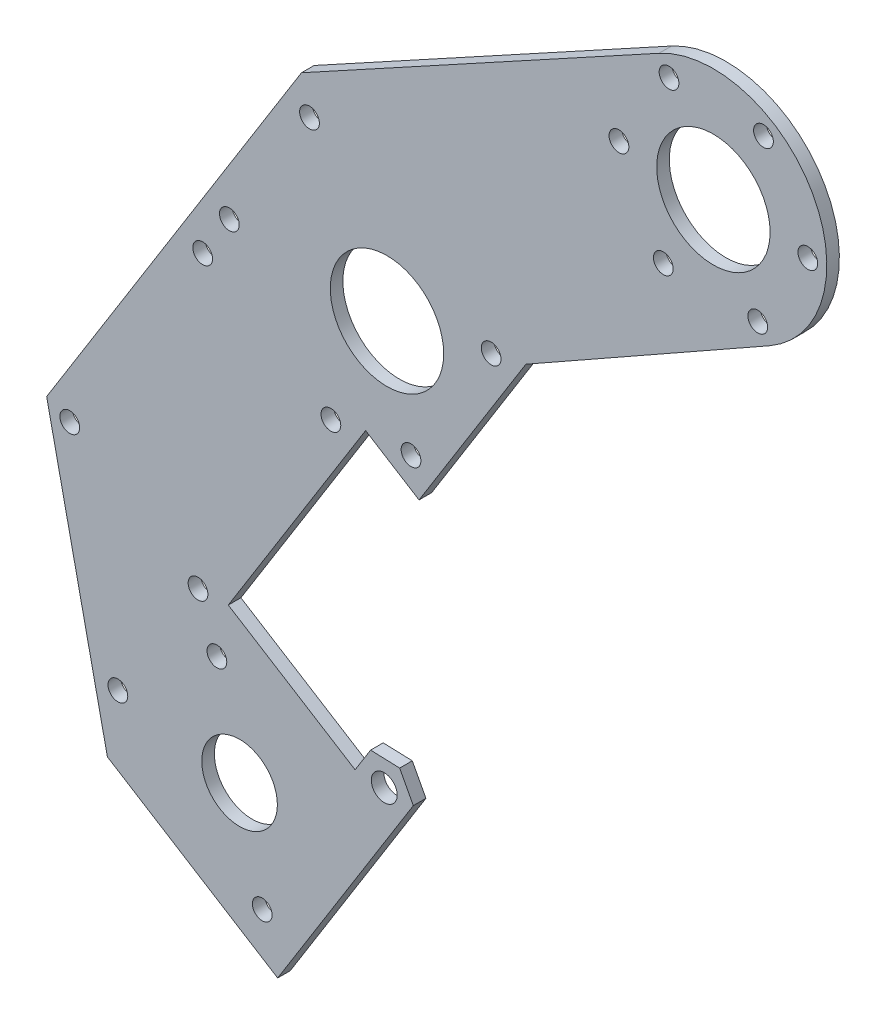
SolidWorks part; units mm, degrees
material "6061 Alloy"
ref_plane "Front Plane" through (0, 0, 0) normal (0, 0, 1) x (1, 0, 0)
ref_plane "Top Plane" through (0, 0, 0) normal (0, 1, 0) x (1, 0, 0)
ref_plane "Right Plane" through (0, 0, 0) normal (1, 0, 0) x (0, 0, -1)
sketch "Sketch1" plane through (0, 0, -14.1946) normal (0, 0, 1) x (1, 0, 0)
  line L0 (-11.4036, 461.0409) -> (18.8813, 509.5069)
  line L1 (-54.3079, 487.8505) -> (-69.6155, 558.824)
  line L2 (8.1111, 516.2368) -> (-23.8465, 536.2061)
  line L3 (10.7592, 591.5868) -> (-157.4902, 322.3315) construction
  line L4 (-11.4036, 461.0409) -> (-54.3079, 487.8505)
  line L5 (-69.6155, 558.824) -> (-5.4017, 661.5875)
  line L6 (-23.8465, 536.2061) -> (10.7592, 591.5868)
  line L8 (-115.7964, 730.5698) -> (48.4493, 627.9377) construction
  line L9 (-142.7163, 687.4889) -> (24.222, 583.1743) construction
  line L10 (51.1419, 626.2552) -> (112.462, 660.9373)
  line L11 (10.7592, 591.5868) -> (24.222, 583.1743)
  line L13 (24.222, 583.1743) -> (51.1419, 626.2552)
  line L16 (-5.4017, 661.5875) -> (84.678, 710.8773)
  line L17 (16.1415, 618.1747) -> (-107.7159, 695.5694) construction
  line L18 (18.8813, 509.5069) -> (22.7847, 515.7536)
  line L19 (-23.8465, 536.2061) -> (-52.9124, 489.691) construction
  line L20 (-4.9986, 524.4287) -> (-34.0645, 477.9135) construction
  line L22 (12.0145, 522.4836) -> (8.1111, 516.2368)
  line L23 (12.0145, 522.4836) -> (19.3423, 522.2277)
  line L24 (19.3423, 522.2277) -> (22.7847, 515.7536)
  line L25 (17.3996, 519.1186) -> (21.0569, 524.9715) construction
  circle A2 centre (16.1415, 618.1747) radius 14.2875
  circle A5 centre (98.3945, 685.8096) radius 14.2875
  arc A7 (112.462, 660.9373) -> (84.678, 710.8773) centre (98.3945, 685.8096) ccw
  circle A8 centre (-107.7159, 695.5694) radius 215.011 construction
  circle A9 centre (-21.0004, 498.8205) radius 9.525
  point P33 (98.3945, 685.8096)
  dimension "D1" = 22.225
  dimension "D2" = 19.05
  dimension "D3" = 7.366
  dimension "D4" = 120
extrude "Boss-Extrude1" add sketch "Sketch1" along normal blind 3.175
sketch "Sketch17" plane through (0, 0, -11.0196) normal (0, 0, 1) x (1, 0, 0)
  line L0 (-4.9986, 524.4287) -> (-34.0645, 477.9135) construction
  line L2 (16.1415, 618.1747) -> (37.6819, 604.7147) construction
  line L11 (-26.7141, 523.5695) -> (-15.2866, 474.0715) construction
  line L12 (24.222, 583.1743) -> (51.1419, 626.2552) construction
  line L13 (37.6819, 604.7147) -> (27.587, 588.5594) construction
  line L14 (27.587, 588.5594) -> (22.2019, 591.9244) construction
  line L15 (22.2019, 591.9244) -> (-28.9566, 623.8918) construction
  line L16 (-5.4017, 661.5875) -> (-69.6155, 558.824) construction
  line L17 (-28.9566, 623.8918) -> (-23.5715, 620.5268) construction
  line L18 (-23.5715, 620.5268) -> (-3.3816, 652.8374) construction
  line L19 (-3.3816, 652.8374) -> (42.3918, 624.2351) construction
  line L20 (10.7592, 591.5868) -> (5.3741, 594.9518) construction
  line L21 (5.3741, 594.9518) -> (-31.4748, 535.9811) construction
  line L22 (-31.4748, 535.9811) -> (-51.6648, 503.6705) construction
  line L23 (5.3741, 594.9518) -> (2.0091, 589.5667) construction
  line L24 (-31.4748, 535.9811) -> (-63.7855, 556.1711) construction
  line L25 (2.0091, 589.5667) -> (-30.3015, 609.7566) construction
  circle A1 centre (-21.0004, 498.8205) radius 25.4 construction
  circle A2 centre (15.4568, 516.0095) radius 6.35 construction
  point P32 (-21.0004, 498.8205)
  dimension "D1" = 45
hole_wizard "#10 Clearance Hole2" positions "Sketch20" profile "Sketch21" hole size "#10" standard "ANSI Inch" end condition through all
sketch "Sketch20" plane through (0, 0, -11.0196) normal (0, 0, 1) x (1, 0, 0)
  point P0 (-26.7141, 523.5695)
  point P3 (-15.2866, 474.0715)
  point P24 (-3.3816, 652.8374)
  point P27 (42.3918, 624.2351)
  point P30 (22.2019, 591.9244)
  point P33 (-23.5715, 620.5268)
  point P42 (-31.4748, 535.9811)
  point P45 (-63.7855, 556.1711)
  point P48 (-51.6648, 503.6705)
  point P54 (2.0091, 589.5667)
  point P57 (-30.3015, 609.7566)
sketch "Sketch21" plane through (-26.7141, 523.5695, -11.0196) normal (1, 0, 0) x (0, -1, 0)
  line L0 (0, 0) -> (0, 3.175)
  line L1 (0, 3.175) -> (2.4892, 3.175)
  line L2 (2.4892, 3.175) -> (2.4892, 0)
  line L5 (2.4892, 0) -> (0, 0)
  line L11 (0, -6.35) -> (0, 107.95) construction
  dimension "Thru Hole Dia." = 4.9784
  dimension "Thru Hole Depth" = 3.175
sketch "Sketch22" plane through (0, 0, -11.0196) normal (0, 0, 1) x (1, 0, 0)
  line L0 (98.3945, 685.8096) -> (111.0132, 706.0038) construction
  line L2 (111.0132, 706.0038) -> (87.2152, 706.8348) construction
  line L3 (87.2152, 706.8348) -> (74.5965, 686.6407) construction
  line L4 (74.5965, 686.6407) -> (85.7758, 665.6155) construction
  line L5 (85.7758, 665.6155) -> (109.5738, 664.7845) construction
  line L6 (109.5738, 664.7845) -> (122.1925, 684.9786) construction
  line L7 (122.1925, 684.9786) -> (111.0132, 706.0038) construction
  circle A0 centre (98.3945, 685.8096) radius 23.8125 construction
hole_wizard "#10 Clearance Hole3" positions "Sketch23" profile "Sketch24" hole size "#10" standard "ANSI Inch" end condition through all
sketch "Sketch23" plane through (0, 0, -11.0196) normal (0, 0, 1) x (1, 0, 0)
  point P0 (111.0132, 706.0038)
  point P3 (122.1925, 684.9786)
  point P6 (109.5738, 664.7845)
  point P9 (85.7758, 665.6155)
  point P12 (74.5965, 686.6407)
  point P15 (87.2152, 706.8348)
sketch "Sketch24" plane through (111.0132, 706.0038, -11.0196) normal (1, 0, 0) x (0, -1, 0)
  line L0 (0, 0) -> (0, 3.175)
  line L1 (0, 3.175) -> (2.4892, 3.175)
  line L2 (2.4892, 3.175) -> (2.4892, 0)
  line L5 (2.4892, 0) -> (0, 0)
  line L11 (0, -6.35) -> (0, 107.95) construction
  dimension "Thru Hole Dia." = 4.9784
  dimension "Thru Hole Depth" = 3.175
hole_wizard "1/4 Clearance Hole1" positions "Sketch25" profile "Sketch26" hole size "1/4" standard "ANSI Inch" end condition through all
sketch "Sketch25" plane through (0, 0, -11.0196) normal (0, 0, 1) x (1, 0, 0)
  point P0 (15.4568, 516.0095)
sketch "Sketch26" plane through (15.4568, 516.0095, -11.0196) normal (1, 0, 0) x (0, -1, 0)
  line L0 (0, 0) -> (0, 3.175)
  line L1 (0, 3.175) -> (3.2639, 3.175)
  line L2 (3.2639, 3.175) -> (3.2639, 0)
  line L5 (3.2639, 0) -> (0, 0)
  line L11 (0, -6.35) -> (0, 107.95) construction
  dimension "Thru Hole Dia." = 6.5278
  dimension "Thru Hole Depth" = 3.175
